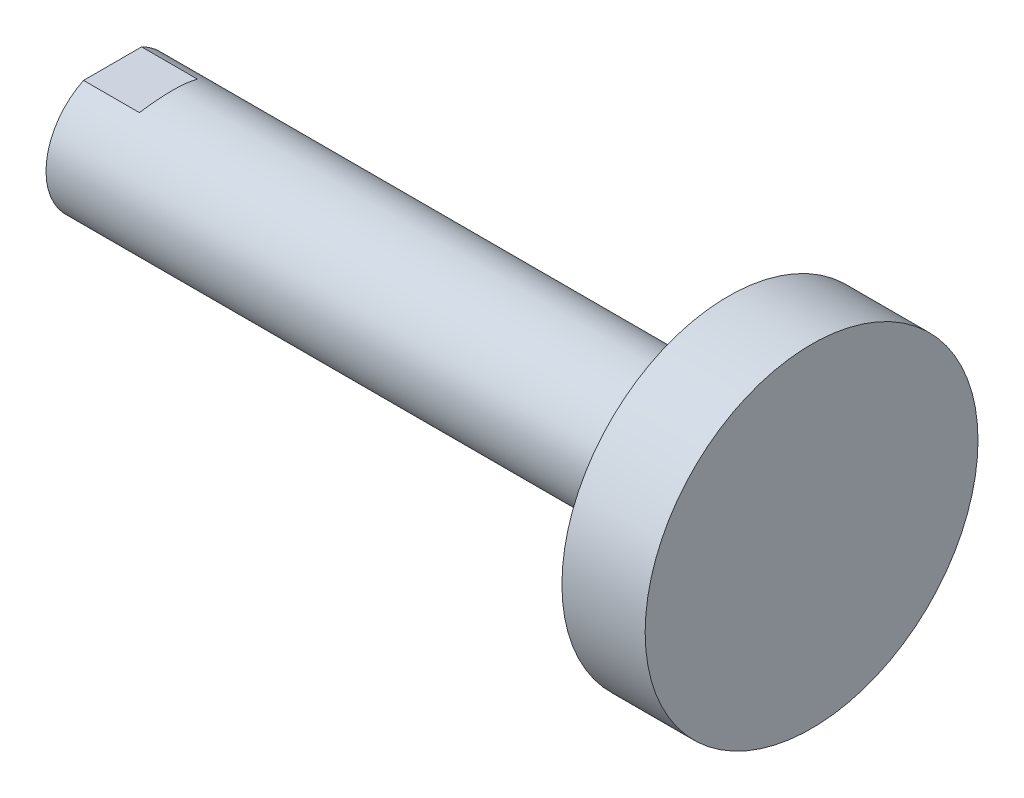
SolidWorks part; units mm, degrees
ref_plane "Ebene vorne" through (0, 0, 0) normal (0, 0, 1) x (1, 0, 0)
ref_plane "Ebene oben" through (0, 0, 0) normal (0, 1, 0) x (1, 0, 0)
ref_plane "Ebene rechts" through (0, 0, 0) normal (1, 0, 0) x (0, 0, -1)
sketch "Skizze1" plane through (0, 0, 0) normal (0, 0, 1) x (1, 0, 0)
  line L0 (-5.5, 0) -> (-5.5, 5)
  line L1 (-5.5, 5) -> (47, 5)
  line L2 (47, 5) -> (47, 0)
  line L3 (47, 0) -> (-5.5, 0)
  line L4 (47, 0) -> (-5.5, 0) construction
revolve "Rotation1" add sketch "Skizze1" angle 360 about L4 reverse direction yes
sketch "Skizze2" plane through (0, 0, 0) normal (0, 0, 1) x (1, 0, 0)
  line L0 (40.75, 0) -> (40.75, 12.5)
  line L1 (40.75, 12.5) -> (47, 12.5)
  line L2 (47, 12.5) -> (47, 0)
  line L3 (47, 0) -> (40.75, 0)
  line L4 (47, 0) -> (40.75, 0) construction
revolve "Rotation2" add sketch "Skizze2" angle 360 about L4 reverse direction yes
ref_plane "Ebene1" through (-5.5, 0, 0) normal (1, 0, 0) x (0, 0, -1)
sketch "Skizze3" plane through (0, 0, 0) normal (0, 0, 1) x (1, 0, 0)
  line L0 (-32, -14.5) -> (4.4735, -14.5)
  line L1 (4.4735, -14.5) -> (-1.3, -4.5)
  line L2 (-1.3, -4.5) -> (-5.5, -4.5)
  line L3 (-5.5, -4.5) -> (-5.5, -9.5)
  line L4 (-5.5, -9.5) -> (-26.5, -9.5)
  line L5 (-26.5, -9.5) -> (-26.5, 9.5)
  line L6 (-26.5, 9.5) -> (-5.5, 9.5)
  line L7 (-5.5, 9.5) -> (-5.5, 4.5)
  line L8 (-5.5, 4.5) -> (-1.3, 4.5)
  line L9 (-1.3, 4.5) -> (4.4735, 14.5)
  line L10 (4.4735, 14.5) -> (-32, 14.5)
  line L11 (-32, 14.5) -> (-32, -14.5)
extrude "Schnitt-Linear austragen1" cut sketch "Skizze3" along normal blind 10 and the other way blind 10
ref_plane "Ebene2" through (47, 0, 0) normal (1, 0, 0) x (0, 0, -1)
sketch "Skizze4" plane through (0, 0, 0) normal (0, 0, 1) x (1, 0, 0)
  line L0 (-5.5, 0) -> (-5.5, 3.6)
  line L1 (-5.5, 3.6) -> (-5.1, 3.2)
  line L2 (-5.1, 3.2) -> (-2.9, 3.2)
  line L3 (-2.9, 3.2) -> (-2.9, 3)
  line L4 (-2.9, 3) -> (-2.3585, 2.4585)
  line L5 (-2.3585, 2.4585) -> (12.5, 2.4585)
  line L6 (12.5, 2.4585) -> (13.9194, 0)
  line L7 (13.9194, 0) -> (-5.5, 0)
  line L8 (13.9194, 0) -> (-5.5, 0) construction
revolve "Schnitt-Rotation1" cut sketch "Skizze4" angle 360 about L8 reverse direction yes
cosmetic thread "Gewindedarstellung1" parameters "D1"=11.4, "D2"=6
ref_plane "Ebene3" through (-11.5, 0, 0) normal (1, 0, 0) x (0, 0, -1)
ref_plane "Ebene4" through (-5.5, 0, 0) normal (1, 0, 0) x (0, 0, -1)
ref_plane "Ebene5" through (0, 0, 0) normal (0, 0, 1) x (1, 0, 0)
ref_plane "FDT_PIRODACC_F1 XY" through (-5.5, 0, 0) normal (-1, 0, 0) x (0, 0, 1)
ref_plane "FDT_PIRODACC_F1 XZ" through (0, 0, 0) normal (0, 0, 1) x (1, 0, 0)
ref_plane "FDT_PIRODACC_F1 YZ" through (0, 0, 0) normal (0, 1, 0) x (1, 0, 0)
ref_axis "FDT_PIRODACC_F1 X" through (-5.5, -50, 0) along (0, 1, 0)
ref_axis "FDT_PIRODACC_F1 Y" through (-5.5, 0, 80.9) along (0, 0, -1)
ref_axis "FDT_PIRODACC_F1 Z" through (-80.9, 0, 0) along (1, 0, 0)
sketch3d "FDT_PIRODACC_F1"
  point P0 (-5.5, 0, 0)
ref_plane "NUT1 XY" through (-11.5, 0, 0) normal (1, 0, 0) x (0, 0, -1)
ref_plane "NUT1 XZ" through (0, 0, 0) normal (0, -1, 0) x (-1, 0, 0)
ref_plane "NUT1 YZ" through (0, 0, 0) normal (0, 0, -1) x (-1, 0, 0)
ref_axis "NUT1 X" through (-11.5, 0, 80.9) along (0, 0, -1)
ref_axis "NUT1 Y" through (-11.5, -50, 0) along (0, 1, 0)
ref_axis "NUT1 Z" through (80.9, 0, 0) along (-1, 0, 0)
sketch3d "NUT1"
  point P0 (-11.5, 0, 0)
ref_plane "PISTON XY" through (47, 0, 0) normal (1, 0, 0) x (0, 0, -1)
ref_plane "PISTON XZ" through (0, 0, 0) normal (0, -1, 0) x (-1, 0, 0)
ref_plane "PISTON YZ" through (0, 0, 0) normal (0, 0, -1) x (-1, 0, 0)
ref_axis "PISTON X" through (47, 0, 80.9) along (0, 0, -1)
ref_axis "PISTON Y" through (47, -50, 0) along (0, 1, 0)
ref_axis "PISTON Z" through (80.9, 0, 0) along (-1, 0, 0)
sketch3d "PISTON"
  point P0 (47, 0, 0)
